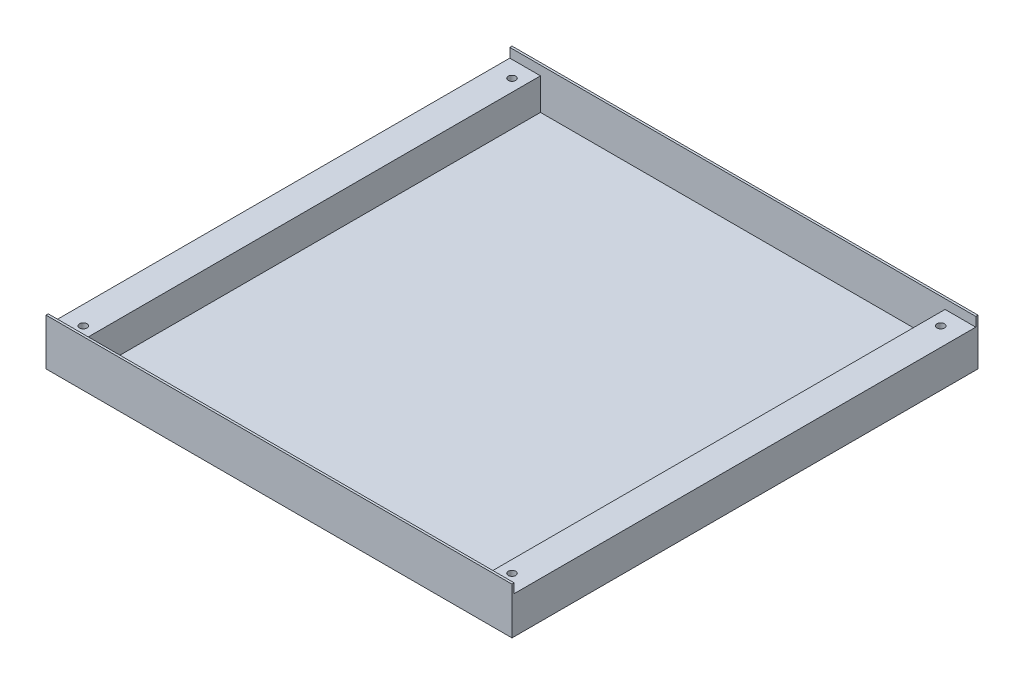
SolidWorks part; units mm, degrees
ref_plane "Plano frontal" through (0, 0, 0) normal (0, 0, 1) x (1, 0, 0)
ref_plane "Plano superior" through (0, 0, 0) normal (0, 1, 0) x (1, 0, 0)
ref_plane "Plano direito" through (0, 0, 0) normal (1, 0, 0) x (0, 0, -1)
sketch "Esboço1" plane through (0, 0, 0) normal (0, 1, 0) x (1, 0, 0)
  line L1 (-125, 125) -> (125, 125)
  line L2 (-125, 125) -> (-125, -125)
  line L3 (-125, -125) -> (125, -125)
  line L4 (125, 125) -> (125, -125)
  line L5 (-125, 125) -> (125, -125) construction
  line L6 (-125, -125) -> (125, 125) construction
  line L9 (-125, 115) -> (-115, 115) construction
  circle A0 centre (-115, 115) radius 2
  circle A1 centre (115, 115) radius 2
  circle A2 centre (-115, -115) radius 2
  circle A3 centre (115, -115) radius 2
  point P0 (0, 0)
  dimension "D1" = 250
  dimension "D2" = 250
extrude "Ressalto-extrusão1" add sketch "Esboço1" along normal blind 3
sketch "Esboço2" plane through (0, 3, 0) normal (0, 1, 0) x (1, 0, 0)
  line L2 (-108.5281, 123.8) -> (-108.5281, -123.8)
  line L3 (-125, -123.8) -> (125, -123.8)
  line L4 (108.5281, 123.8) -> (108.5281, -123.8)
  line L5 (-125, -123.8) -> (-125, 123.8)
  line L6 (-125, 123.8) -> (125, 123.8)
  line L7 (125, -123.8) -> (125, 123.8)
  line L8 (-125, -125) -> (125, -125)
  line L9 (-125, -125) -> (-125, 125)
  line L10 (-125, 125) -> (125, 125)
  line L11 (125, -125) -> (125, 125)
  line L12 (-125, -123.8) -> (125, 123.8) construction
  line L13 (-125, 123.8) -> (125, -123.8) construction
  point P0 (0, 0)
  point P8 (0, 0)
  point P14 (0, 0)
  circle M3 centre (-115, -115) radius 2
  circle M4 centre (-115, 115) radius 2
  line M5 (125, -125) -> (125, 125)
  line M6 (125, 125) -> (-125, 125)
  line M7 (-125, 125) -> (-125, -125)
  line M8 (-125, -125) -> (125, -125)
  circle M9 centre (115, 115) radius 2
  circle M10 centre (115, -115) radius 2
  dimension "D1" = 1.2
extrude "Ressalto-extrusão2" add sketch "Esboço2" along normal blind 17 contours L6 L3 L2 M7 M3 M4 | L6 L4 L3 M5 M9 M10 region at (-116.775, 3, 0) region at (116.775, 3, 0)
extrude "Ressalto-extrusão3" add sketch "Esboço2<5>" along normal blind 22 contours L6 M7 M5 M6 | L3 M7 M8 M5 region at (0, 3, -124.4) region at (0, 3, 124.4)
sketch "Esboço2<5>" plane through (0, 3, 0) normal (0, 1, 0) x (1, 0, 0) same geometry as "Esboço2"
